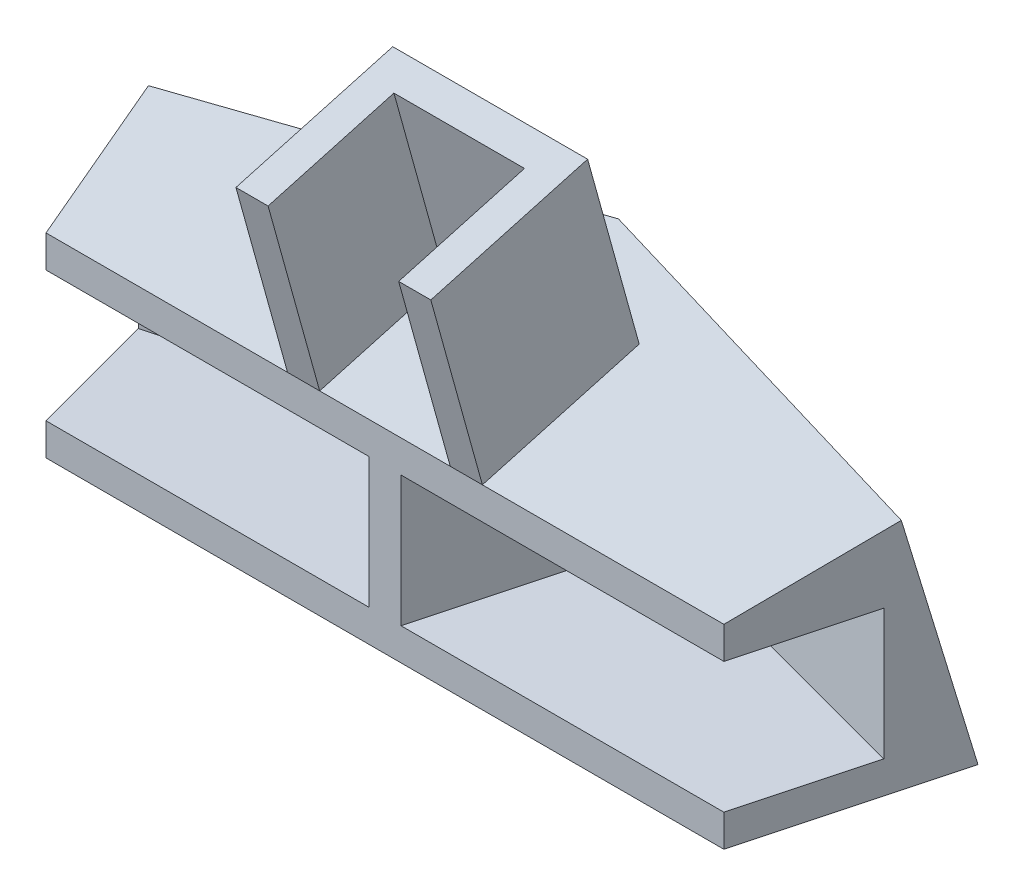
SolidWorks part; units mm, degrees
ref_plane "Front Plane" through (0, 0, 0) normal (0, 0, 1) x (1, 0, 0)
ref_plane "Top Plane" through (0, 0, 0) normal (0, 1, 0) x (1, 0, 0)
ref_plane "Right Plane" through (0, 0, 0) normal (1, 0, 0) x (0, 0, -1)
sketch "Sketch4" plane through (0, 0, 0) normal (0, 1, 0) x (1, 0, 0)
  line L0 (0, 0) -> (0, -14.1213) construction
  line L1 (-52.7015, -14.1213) -> (52.7015, -14.1213) construction
  line L2 (0, 0) -> (-52.7015, -14.1213) construction
  line L3 (0, 0) -> (52.7015, -14.1213) construction
  line L4 (52.7015, -14.1213) -> (57.9555, 5.487) construction
  line L5 (-52.7015, -14.1213) -> (-57.9555, 5.487) construction
  line L6 (0, 0) -> (0, 21.0161) construction
  line L7 (57.9555, 5.487) -> (0, 21.0161) construction
  line L8 (-57.9555, 5.487) -> (0, 21.0161) construction
  line L9 (-57.9555, 5.487) -> (-63.1319, 24.8055) construction
  line L10 (57.9555, 5.487) -> (63.1319, 24.8055) construction
  line L11 (-63.1319, 24.8055) -> (0, 41.7216) construction
  line L12 (0, 41.7216) -> (63.1319, 24.8055) construction
  line L13 (0, 21.0161) -> (0, 41.7216)
  arc A0 (-15.1096, -4.0486) -> (15.1096, -4.0486) centre (0, 0) ccw construction
sketch "Sketch8" plane through (0, 0, 0) normal (0, 1, 0) x (1, 0, 0)
  line L0 (-63.1319, 24.8055) -> (-52.7015, -14.1213)
  line L1 (-52.7015, -14.1213) -> (52.7015, -14.1213) construction
  line L2 (52.7015, -14.1213) -> (63.1319, 24.8055) construction
  line L3 (63.1319, 24.8055) -> (0, 41.7216) construction
  line L4 (0, 41.7216) -> (-63.1319, 24.8055)
  line L5 (0, 41.7216) -> (0, -14.1213)
  line L6 (0, -14.1213) -> (-52.7015, -14.1213)
extrude "Boss-Extrude5" add sketch "Sketch8" along normal blind 5
sketch "Sketch9" plane through (0, 5, 0) normal (0, 1, 0) x (1, 0, 0)
  line L0 (-63.1319, 24.8055) -> (-57.9555, 5.487)
  line L1 (-57.9555, 5.487) -> (0, 21.0161)
  line L2 (-63.1319, 24.8055) -> (0, 41.7216)
  line L6 (0, 41.7216) -> (0, 21.0161)
extrude "Boss-Extrude6" add sketch "Sketch9" along normal blind 20.3
sketch "Sketch10" plane through (0, 25.3, 0) normal (0, 1, 0) x (1, 0, 0)
  line L7 (0, 41.7216) -> (0, -14.1213)
  line L8 (0, -14.1213) -> (-52.7015, -14.1213)
  line L9 (-52.7015, -14.1213) -> (-63.1319, 24.8055)
  line L10 (-63.1319, 24.8055) -> (0, 41.7216)
extrude "Boss-Extrude7" add sketch "Sketch10" along normal blind 20
sketch "Sketch19" plane through (-52.7015, 0, 14.1213) normal (-0.9659, 0, 0.2588) x (0.2588, 0, 0.9659)
  line L0 (-20.3, 25.3) -> (-25.1296, 26.5941) construction
  line L1 (-32.2555, 0) -> (-20.1174, 45.3)
  line L2 (-40.3, 0) -> (0, 0) construction
  line L3 (-40.3, 45.3) -> (0, 45.3) construction
  line L4 (-20.1174, 45.3) -> (-40.3, 45.3)
  line L5 (-40.3, 45.3) -> (-40.3, 0)
  line L6 (-40.3, 0) -> (-32.2555, 0)
  line L7 (-20.1174, 45.3) -> (-20.1174, 0) construction
  arc A0 (-17.2193, 56.116) -> (-20.1174, 34.1025) centre (-20.1174, 45.3) ccw construction
extrude "Cut-Extrude1" cut sketch "Sketch19" against normal through all
sketch "Sketch22" plane through (0, 0, 0) normal (1, 0, 0) x (0, 0, -1)
  line L0 (-14.1213, 25.3) -> (-14.1213, 30.3) construction
  line L1 (-14.1213, 45.3) -> (-14.1213, 25.3) construction
  line L2 (-14.1213, 30.3) -> (22.1936, 40.3738)
  line L3 (33.3933, 0) -> (20.8271, 45.3) construction
  line L4 (-14.1213, 30.3) -> (-14.1213, 45.3)
  line L5 (-14.1213, 45.3) -> (20.8271, 45.3)
  line L6 (20.8271, 45.3) -> (22.1936, 40.3738)
extrude "Cut-Extrude3" cut sketch "Sketch22" against normal through all
sketch "Sketch23" plane through (0, 31.7723, 8.8137) normal (0, 0.9636, 0.2673) x (1, 0, 0)
  line L0 (-10.15, -5.5081) -> (-15.15, -5.5081)
  line L1 (-52.7015, -5.5081) -> (0, -5.5081) construction
  line L2 (-10.15, -5.5081) -> (-10.15, 14.7919)
  line L3 (-10.15, 14.7919) -> (0, 14.7919)
  line L4 (0, -5.5081) -> (0, 32.1782) construction
  line L5 (-15.15, -5.5081) -> (-15.15, 19.7919)
  line L6 (-15.15, 19.7919) -> (0, 19.7919)
  line L7 (0, 19.7919) -> (0, 14.7919)
extrude "Boss-Extrude9" add sketch "Sketch23" along normal blind 30
sketch "Sketch24" plane through (0, 5, 0) normal (0, 1, 0) x (1, 0, 0)
  line L0 (0, 21.0161) -> (-2.5, 20.3462) construction
  line L2 (-57.9555, 5.487) -> (0, 21.0161) construction
  line L4 (-2.5, 20.3462) -> (-2.5, -14.1213) construction
  line L5 (-52.7015, -14.1213) -> (0, -14.1213) construction
  line L7 (-2.5, -14.1213) -> (0, -14.1213) construction
  line L8 (0, -14.1213) -> (0, 21.0161) construction
  line L9 (-2.5, -14.1213) -> (-11.1169, 18.0373)
  line L10 (-11.1169, 18.0373) -> (0, 21.0161)
  line L11 (0, 21.0161) -> (0, -14.1213)
  line L12 (-2.5, -14.1213) -> (0, -14.1213)
extrude "Boss-Extrude11" add sketch "Sketch24" along normal up to surface (20.3 mm away) up to face at (-27.6643, 25.3, 0.4349)
mirror "Mirror1" about plane through (0, 5, -41.7216) normal (-1, 0, 0) of "Boss-Extrude11", "Boss-Extrude9", "Cut-Extrude3", "Cut-Extrude1", "Boss-Extrude7", "Boss-Extrude6", "Boss-Extrude5"
